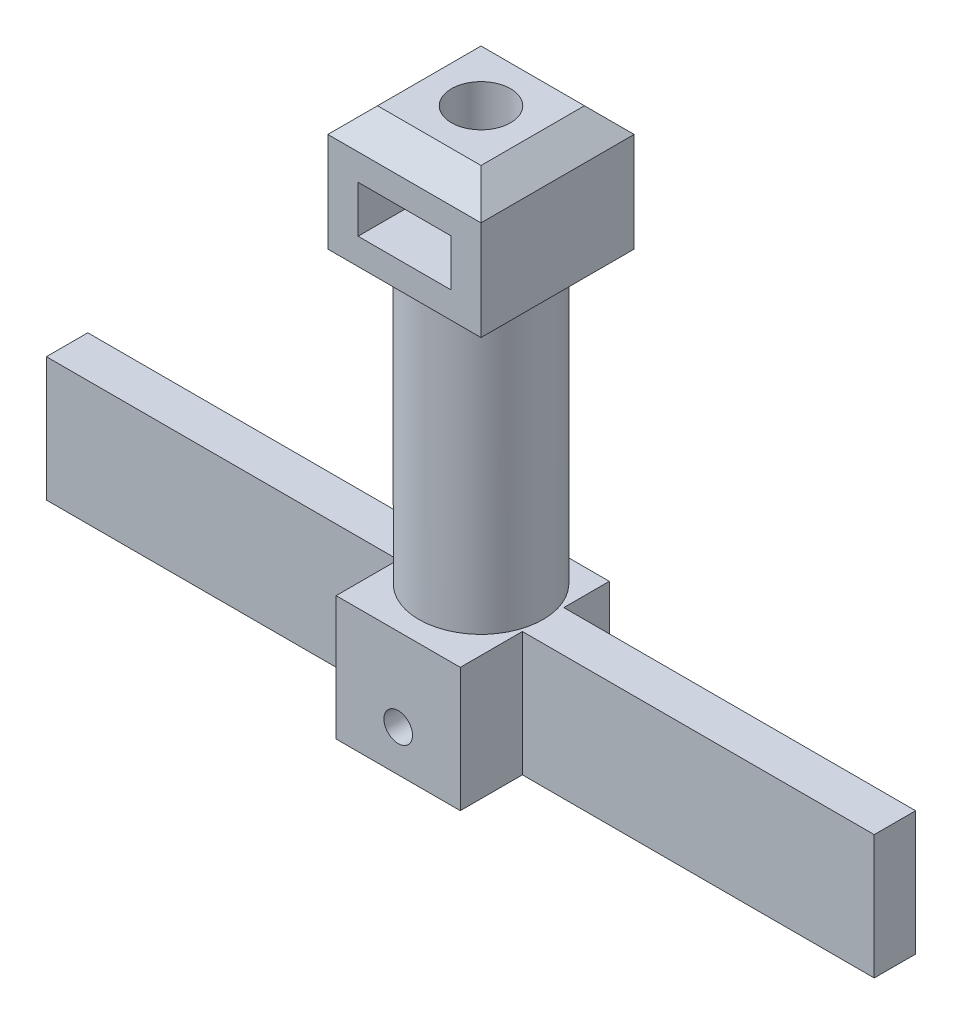
SolidWorks part; units mm, degrees
ref_plane "Front Plane" through (0, 0, 0) normal (0, 0, 1) x (1, 0, 0)
ref_plane "Top Plane" through (0, 0, 0) normal (0, 1, 0) x (1, 0, 0)
ref_plane "Right Plane" through (0, 0, 0) normal (1, 0, 0) x (0, 0, -1)
sketch "Sketch1" plane through (0, 0, 0) normal (0, 1, 0) x (1, 0, 0)
  line L1 (0, 0) -> (100, 0)
  line L2 (0, 0) -> (0, 10)
  line L3 (0, 10) -> (100, 10)
  line L4 (100, 0) -> (100, 10)
  dimension "D1" = 100
  dimension "D2" = 10
extrude "Boss-Extrude1" add sketch "Sketch1" along normal blind 15
sketch "Sketch2" plane through (0, 15, 0) normal (0, 1, 0) x (1, 0, 0)
  line L0 (100, 10) -> (0, 10) construction
  line L1 (100, 0) -> (100, 10) construction
  circle A0 centre (50, 5) radius 7.5
  dimension "D2" = 15
  dimension "D3" = 50
  dimension "D1" = 5
extrude "Boss-Extrude2" add sketch "Sketch2" along normal blind 30
sketch "Sketch3" plane through (0, 45, 0) normal (0, 1, 0) x (1, 0, 0)
  line L1 (40.75, 14.25) -> (59.25, 14.25)
  line L2 (40.75, 14.25) -> (40.75, -4.25)
  line L3 (40.75, -4.25) -> (59.25, -4.25)
  line L4 (59.25, 14.25) -> (59.25, -4.25)
  circle A0 centre (50, 5) radius 7.5 construction
  circle A1 centre (50, 5) radius 7.5 construction
  dimension "D4" = 9.25
  dimension "D1" = 18.5
  dimension "D2" = 18.5
  dimension "D3" = 9.25
extrude "Boss-Extrude3" add sketch "Sketch3" along normal blind 20
chamfer "Chamfer1" distance 3 angle 45 4 edges at (50, 65, -14.25) (59.25, 65, -5) (50, 65, 4.25) (40.75, 65, -5)
chamfer "Chamfer2" distance 5 angle 45 4 edges at (50, 45, -14.25) (40.75, 45, -5) (59.25, 45, -5) (50, 45, 4.25)
sketch "Sketch4" plane through (0, 0, 4.25) normal (0, 0, 1) x (1, 0, 0)
  line L0 (59.25, 62) -> (40.75, 62) construction
  line L1 (44.4, 58.825) -> (55.6, 58.825)
  line L2 (44.4, 58.825) -> (44.4, 53.175)
  line L3 (44.4, 53.175) -> (55.6, 53.175)
  line L4 (55.6, 58.825) -> (55.6, 53.175)
  line L5 (40.75, 50) -> (59.25, 50) construction
  line L6 (59.25, 62) -> (59.25, 50) construction
  line L7 (40.75, 62) -> (40.75, 50) construction
  dimension "D1" = 11.2
  dimension "D2" = 5.65
  dimension "D3" = 3.175
  dimension "D4" = 3.175
  dimension "D5" = 3.65
  dimension "D6" = 3.65
extrude "Cut-Extrude1" cut sketch "Sketch4" against normal through all
hole_wizard "1/4 Clearance Hole1" positions "Sketch6" profile "Sketch7" hole size "1/4" standard "ANSI Inch"
sketch "Sketch6" plane through (0, 65, 0) normal (0, 1, 0) x (1, 0, 0)
  line L0 (56.25, 11.25) -> (43.75, 11.25) construction
  line L1 (43.75, -1.25) -> (56.25, -1.25) construction
  line L2 (56.25, -1.25) -> (56.25, 11.25) construction
  point P0 (50, 5)
  dimension "D1" = 6.25
  dimension "D2" = 6.25
  dimension "D3" = 6.25
sketch "Sketch7" plane through (50, 65, -5) normal (1, 0, 0) x (0, 0, 1)
  line L0 (0, 0) -> (0, 27.1458)
  line L1 (0, 27.1458) -> (3.5712, 25)
  line L2 (3.5712, 25) -> (3.5712, 0)
  line L5 (3.5712, 0) -> (0, 0)
  line L10 (0, 27.1458) -> (-3.5712, 25) construction
  line L11 (0, -6.35) -> (0, 107.95) construction
  dimension "Hole Dia." = 7.1425
  dimension "Hole Depth" = 25
  dimension "Drill Angle" = 118
sketch "Sketch8" plane through (0, 0, 0) normal (0, 0, 1) x (1, 0, 0)
  line L0 (0, 15) -> (44.4098, 15) construction
  line L1 (42.5, 15) -> (57.5, 15)
  line L2 (42.5, 15) -> (42.5, 0)
  line L3 (42.5, 0) -> (57.5, 0)
  line L4 (57.5, 15) -> (57.5, 0)
  line L5 (0, 0) -> (100, 0) construction
  line L6 (0, 15) -> (0, 0) construction
  line L7 (100, 15) -> (100, 0) construction
  point P8 (0, 7.5)
  dimension "D1" = 15
  dimension "D2" = 42.5
  dimension "D3" = 42.5
extrude "Boss-Extrude4" add sketch "Sketch8" along normal blind 5
sketch "Sketch9" plane through (0, 0, 0) normal (0, -1, 0) x (1, 0, 0)
  circle A0 centre (50, -5) radius 2.65
  dimension "D1" = 5.3
extrude "Cut-Extrude2" cut sketch "Sketch9" against normal blind 25
hole_wizard "#4 Clearance Hole1" positions "Sketch12" profile "Sketch11" hole size "#4" standard "ANSI Inch"
sketch "Sketch12" plane through (0, 0, 5) normal (0, 0, 1) x (1, 0, 0)
  line L0 (50, 25) -> (50, 0) construction
  line L1 (42.5, 0) -> (57.5, 0) construction
  point P0 (50, 5)
  dimension "D1" = 5
sketch "Sketch11" plane through (50, 5, 5) normal (1, 0, 0) x (0, -1, 0)
  line L0 (0, 0) -> (0, 11.0378)
  line L1 (0, 11.0378) -> (1.7272, 10)
  line L2 (1.7272, 10) -> (1.7272, 0)
  line L5 (1.7272, 0) -> (0, 0)
  line L10 (0, 11.0378) -> (-1.7272, 10) construction
  line L11 (0, -6.35) -> (0, 107.95) construction
  dimension "Hole Dia." = 3.4544
  dimension "Hole Depth" = 10
  dimension "Drill Angle" = 118
sketch "Sketch13" plane through (0, 0, 0) normal (0, -1, 0) x (1, 0, 0)
  line L0 (42.5, 5) -> (57.5, 5) construction
  line L1 (46.7, 2.5) -> (53.3, 2.5)
  line L2 (46.7, 2.5) -> (46.7, -0.29)
  line L3 (46.7, -0.29) -> (53.3, -0.29)
  line L4 (53.3, 2.5) -> (53.3, -0.29)
  line L5 (50, -2.9902) -> (50, 5) construction
  dimension "D1" = 6.6
  dimension "D2" = 2.79
  dimension "D3" = 2.5
  dimension "D4" = 3.3
extrude "Cut-Extrude3" cut sketch "Sketch13" against normal blind 7.7559
sketch "Sketch14" plane through (0, 0, -10) normal (0, 0, -1) x (-1, 0, 0)
  line L1 (-57.5, 15) -> (-42.5, 15)
  line L2 (-57.5, 15) -> (-57.5, 0)
  line L3 (-57.5, 0) -> (-42.5, 0)
  line L4 (-42.5, 15) -> (-42.5, 0)
extrude "Boss-Extrude5" add sketch "Sketch14" along normal blind 3
sketch "Sketch15" plane through (100, 0, 0) normal (1, 0, 0) x (0, 0, -1)
  line L0 (0, 0) -> (10, 0) construction
  line L1 (0, 15) -> (2.5, 15)
  line L2 (0, 15) -> (0, 0)
  line L3 (0, 0) -> (2.5, 0)
  line L4 (2.5, 15) -> (2.5, 0)
  line L6 (10, 15) -> (7.5, 15)
  line L7 (10, 15) -> (10, 0)
  line L8 (10, 0) -> (7.5, 0)
  line L9 (7.5, 15) -> (7.5, 0)
  dimension "D1" = 5
  dimension "D2" = 2.5
extrude "Cut-Extrude4" cut sketch "Sketch15" against normal up to surface (42.5 mm away) up to face at (57.5, 7.5, 2.5)
sketch "Sketch16" plane through (0, 0, 0) normal (-1, 0, 0) x (0, 0, 1)
  line L0 (-10, 0) -> (0, 0) construction
  line L1 (-10, 15) -> (-7.5, 15)
  line L2 (-10, 15) -> (-10, 0)
  line L3 (-10, 0) -> (-7.5, 0)
  line L4 (-7.5, 15) -> (-7.5, 0)
  line L6 (0, 15) -> (-2.5, 15)
  line L7 (0, 15) -> (0, 0)
  line L8 (0, 0) -> (-2.5, 0)
  line L9 (-2.5, 15) -> (-2.5, 0)
  dimension "D1" = 2.5
  dimension "D2" = 5
extrude "Cut-Extrude5" cut sketch "Sketch16" against normal up to surface (42.5 mm away) up to face at (42.5, 7.5, -11.5)
equation "\"D3@Sketch3\"=\"D1@Sketch3\"*.5"
equation "\"D4@Sketch3\"=\"D3@Sketch3\""
equation "\"D4@Sketch13\"=0.5*\"D1@Sketch13\""
